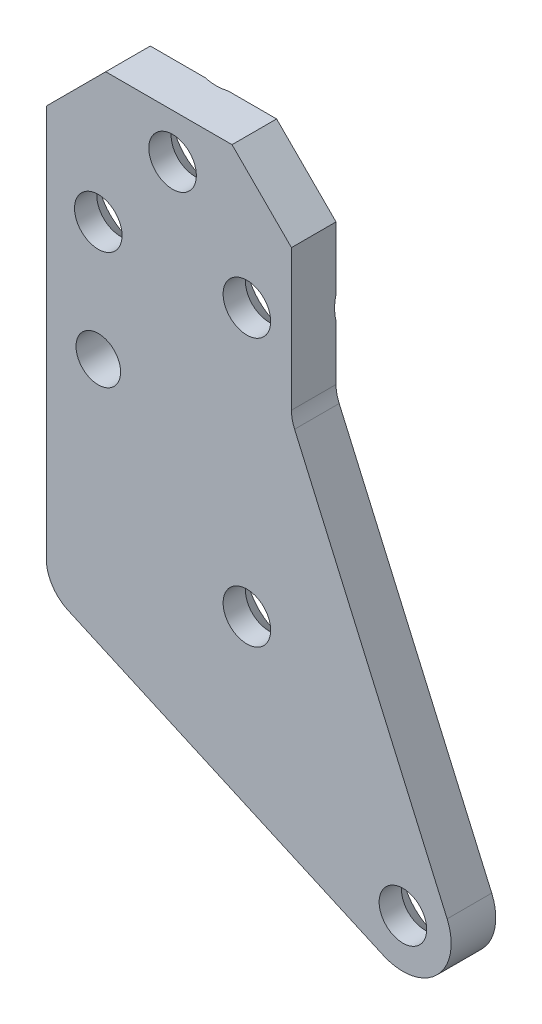
SolidWorks part; units mm, degrees
ref_plane "前视基准面" through (0, 0, 0) normal (0, 0, 1) x (1, 0, 0)
ref_plane "上视基准面" through (0, 0, 0) normal (0, 1, 0) x (1, 0, 0)
ref_plane "右视基准面" through (0, 0, 0) normal (1, 0, 0) x (0, 0, -1)
sketch "草图1" plane through (0, 0, 0) normal (0, 0, 1) x (1, 0, 0)
  line L0 (-3.5, 17) -> (-3.5, -15)
  line L1 (0, 0) -> (7.6906, 0) construction
  line L2 (7.6906, 0) -> (20.5, -22.1865) construction
  line L3 (-3.5, 17) -> (13, 17)
  line L4 (13, 17) -> (13, 3)
  line L5 (-3.5, -15) -> (19.1717, -25.1527)
  line L6 (13, 3) -> (23.4762, -20.8809)
  circle A0 centre (0, 0) radius 1.5
  circle A1 centre (10, -10) radius 1.6
  circle A2 centre (20.5, -22.1865) radius 1.6
  circle A3 centre (10, -4) radius 1.6 construction
  circle A4 centre (10, -10) radius 2.5 construction
  arc A5 (19.1717, -25.1527) -> (23.4762, -20.8809) centre (20.5, -22.1865) ccw
  circle A6 centre (0, 8) radius 1.6
  circle A7 centre (10, 8) radius 1.6
  circle A8 centre (5, 14) radius 1.6
  dimension "D1" = 3
  dimension "D4" = 3.2
  dimension "D6" = 3.2
  dimension "D9" = 5
  dimension "D11" = 6.5
  dimension "D2" = 10
  dimension "D3" = 10
  dimension "D5" = 3.5
  dimension "D7" = 30
  dimension "D8" = 4
  dimension "D10" = 21
  dimension "D12" = 3
  dimension "D13" = 10
  dimension "D14" = 5
  dimension "D15" = 6
  dimension "D16" = 3
  dimension "D17" = 5
  dimension "D18" = 3
  dimension "D19" = 15
extrude "凸台-拉伸1" add sketch "草图1" along normal mid plane 3
chamfer "倒角1" distance 1.5 angle 45 5 edges at (1.6, 8, -1.5) (6.6, 14, -1.5) (11.6, 8, -1.5) (11.6, -10, -1.5) (22.1, -22.1865, -1.5)
fillet "圆角1" radius 2.5 2 edges at (13, 3, 0) (-3.5, -15, 0)
chamfer "倒角2" distance 4 angle 45 2 edges at (13, 17, 0) (-3.5, 17, 0)
equation "\"D14@草图1\"=\"D13@草图1\"/2"
